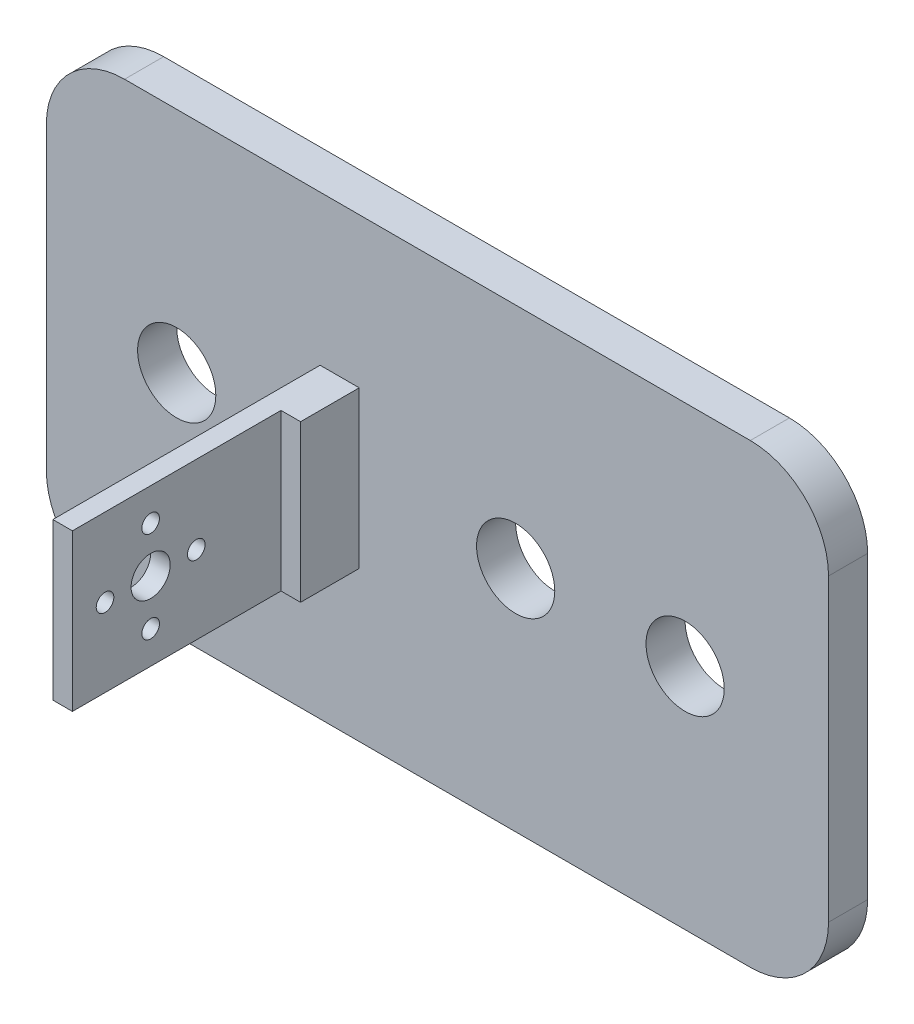
SolidWorks part; units mm, degrees
ref_plane "Front Plane" through (0, 0, 0) normal (0, 0, 1) x (1, 0, 0)
ref_plane "Top Plane" through (0, 0, 0) normal (0, 1, 0) x (1, 0, 0)
ref_plane "Right Plane" through (0, 0, 0) normal (1, 0, 0) x (0, 0, -1)
ref_plane "PZ_m35_000" through (0, 0, -35) normal (0, 0, 1) x (1, 0, 0)
sketch "S_box1" plane through (0, 0, -35) normal (0, 0, 1) x (1, 0, 0)
  line L0 (-62, -35) -> (58, -35)
  line L1 (58, -35) -> (58, 35)
  line L2 (58, 35) -> (-62, 35)
  line L3 (-62, 35) -> (-62, -35)
  dimension "P1" = 62
  dimension "P2" = 35
  dimension "P3" = 58
  dimension "P4" = 35
  dimension "P5" = 58
  dimension "P6" = 35
  dimension "P7" = 62
  dimension "P8" = 35
extrude "Boss_1" add sketch "S_box1" along normal blind 6
ref_plane "PZ_m29_500" through (0, 0, -29.5) normal (0, 0, 1) x (1, 0, 0)
sketch "S_box2" plane through (0, 0, -29.5) normal (0, 0, 1) x (1, 0, 0)
  line L0 (-20, -12) -> (-17, -12)
  line L1 (-17, -12) -> (-17, 12)
  line L2 (-17, 12) -> (-20, 12)
  line L3 (-20, 12) -> (-20, -12)
  dimension "P1" = 20
  dimension "P2" = 12
  dimension "P3" = 17
  dimension "P4" = 12
  dimension "P5" = 17
  dimension "P6" = 12
  dimension "P7" = 20
  dimension "P8" = 12
extrude "Boss_2" add sketch "S_box2" along normal blind 41.5
sketch "S_box3" plane through (0, 0, -29.5) normal (0, 0, 1) x (1, 0, 0)
  line L0 (-17.5, -12) -> (-14, -12)
  line L1 (-14, -12) -> (-14, 12)
  line L2 (-14, 12) -> (-17.5, 12)
  line L3 (-17.5, 12) -> (-17.5, -12)
  dimension "P1" = 17.5
  dimension "P2" = 12
  dimension "P3" = 14
  dimension "P4" = 12
  dimension "P5" = 14
  dimension "P6" = 12
  dimension "P7" = 17.5
  dimension "P8" = 12
extrude "Boss_3" add sketch "S_box3" along normal blind 9.5
ref_plane "PX_m20_100" through (-20.1, 0, 0) normal (1, 0, 0) x (0, 0, -1)
sketch "S_hole4" plane through (-20.1, 0, 0) normal (1, 0, 0) x (0, 0, -1)
  circle A0 centre (0, 0) radius 3
  dimension "D1_S_hole4" = 6
extrude "Hole_4" cut sketch "S_hole4" along normal blind 3.2
sketch "S_hole5" plane through (-20.1, 0, 0) normal (1, 0, 0) x (0, 0, -1)
  circle A0 centre (0, 7) radius 1.35
  dimension "D1_S_hole5" = 2.7
  dimension "P2" = 7
extrude "Hole_5" cut sketch "S_hole5" along normal blind 3.2
sketch "S_hole6" plane through (-20.1, 0, 0) normal (1, 0, 0) x (0, 0, -1)
  circle A0 centre (-7, 0) radius 1.35
  dimension "D1_S_hole6" = 2.7
  dimension "P2" = 7
extrude "Hole_6" cut sketch "S_hole6" along normal blind 3.2
sketch "S_hole7" plane through (-20.1, 0, 0) normal (1, 0, 0) x (0, 0, -1)
  circle A0 centre (0, -7) radius 1.35
  dimension "D1_S_hole7" = 2.7
  dimension "P2" = 7
extrude "Hole_7" cut sketch "S_hole7" along normal blind 3.2
sketch "S_hole8" plane through (-20.1, 0, 0) normal (1, 0, 0) x (0, 0, -1)
  circle A0 centre (7, 0) radius 1.35
  dimension "D1_S_hole8" = 2.7
  dimension "P2" = 7
extrude "Hole_8" cut sketch "S_hole8" along normal blind 3.2
ref_plane "PZ_m35_100" through (0, 0, -35.1) normal (0, 0, 1) x (1, 0, 0)
sketch "S_hole9" plane through (0, 0, -35.1) normal (0, 0, 1) x (1, 0, 0)
  circle A0 centre (-42, 0) radius 6
  dimension "D1_S_hole9" = 12
  dimension "P2" = 42
extrude "Hole_9" cut sketch "S_hole9" along normal blind 6.2
sketch "S_hole10" plane through (0, 0, -35.1) normal (0, 0, 1) x (1, 0, 0)
  circle A0 centre (10, 0) radius 6
  dimension "D1_S_hole10" = 12
  dimension "P2" = 10
extrude "Hole_10" cut sketch "S_hole10" along normal blind 6.2
sketch "S_hole11" plane through (0, 0, -35.1) normal (0, 0, 1) x (1, 0, 0)
  circle A0 centre (36, 0) radius 6
  dimension "D1_S_hole11" = 12
  dimension "P2" = 36
extrude "Hole_11" cut sketch "S_hole11" along normal blind 6.2
sketch "S_pcut12" plane through (0, 0, -35.1) normal (0, 0, 1) x (1, 0, 0)
  line L0 (58.6, 35.6) -> (46, 35.6)
  line L1 (46, 35.6) -> (46, 35)
  line L2 (58, 23) -> (58.6, 23)
  line L3 (58.6, 23) -> (58.6, 35.6)
  arc A0 (46, 35) -> (58, 23) centre (46.0001, 23.0001) cw
extrude "Cut_12" cut sketch "S_pcut12" along normal blind 6.2
sketch "S_pcut13" plane through (0, 0, -35.1) normal (0, 0, 1) x (1, 0, 0)
  line L0 (58.6, -35.6) -> (46, -35.6)
  line L1 (46, -35.6) -> (46, -35)
  line L2 (58, -23) -> (58.6, -23)
  line L3 (58.6, -23) -> (58.6, -35.6)
  arc A0 (46, -35) -> (58, -23) centre (46.0001, -23.0001) ccw
extrude "Cut_13" cut sketch "S_pcut13" along normal blind 6.2
sketch "S_pcut14" plane through (0, 0, -35.1) normal (0, 0, 1) x (1, 0, 0)
  line L0 (-62.6, 35.6) -> (-50, 35.6)
  line L1 (-50, 35.6) -> (-50, 35)
  line L2 (-62, 23) -> (-62.6, 23)
  line L3 (-62.6, 23) -> (-62.6, 35.6)
  arc A0 (-50, 35) -> (-62, 23) centre (-50.0001, 23.0001) ccw
extrude "Cut_14" cut sketch "S_pcut14" along normal blind 6.2
sketch "S_pcut15" plane through (0, 0, -35.1) normal (0, 0, 1) x (1, 0, 0)
  line L0 (-62.6, -35.6) -> (-50, -35.6)
  line L1 (-50, -35.6) -> (-50, -35)
  line L2 (-62, -23) -> (-62.6, -23)
  line L3 (-62.6, -23) -> (-62.6, -35.6)
  arc A0 (-50, -35) -> (-62, -23) centre (-50.0001, -23.0001) cw
extrude "Cut_15" cut sketch "S_pcut15" along normal blind 6.2
equation "\"plate_t\" = 3"
equation "\"clearance\" = 0.4"
